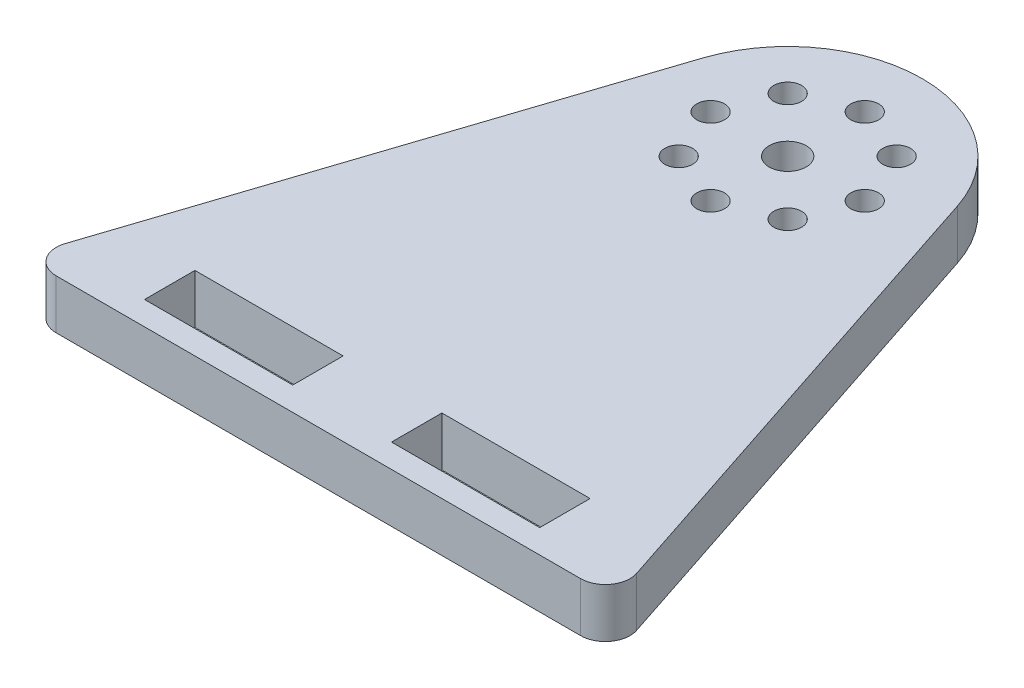
SolidWorks part; units mm, degrees
ref_plane "Front Plane" through (0, 0, 0) normal (0, 0, 1) x (1, 0, 0)
ref_plane "Top Plane" through (0, 0, 0) normal (0, 1, 0) x (1, 0, 0)
ref_plane "Right Plane" through (0, 0, 0) normal (1, 0, 0) x (0, 0, -1)
sketch "Sketch1" plane through (0, 0, 0) normal (0, 1, 0) x (1, 0, 0)
  line L0 (0, 0) -> (0, -60.325) construction
  line L1 (-38.1, -60.325) -> (38.1, -60.325)
  line L2 (0, 0) -> (-38.1, -60.325) construction
  line L3 (0, 0) -> (38.1, -60.325) construction
  line L4 (-46.9823, 0) -> (46.9823, 0) construction
  line L5 (-38.1, -60.325) -> (-16.4346, 5.4161)
  line L6 (38.1, -60.325) -> (16.4346, 5.4161)
  line L7 (34.961, -50.8) -> (-34.961, -50.8) construction
  line L8 (6.35, -50.8) -> (6.35, -57.277)
  line L9 (-25.4, -50.8) -> (-6.35, -50.8)
  line L10 (-25.4, -50.8) -> (-25.4, -57.277)
  line L11 (-25.4, -57.277) -> (-6.35, -57.277)
  line L12 (-6.35, -50.8) -> (-6.35, -57.277)
  line L13 (25.4, -57.277) -> (6.35, -57.277)
  line L14 (25.4, -50.8) -> (25.4, -57.277)
  line L15 (25.4, -50.8) -> (6.35, -50.8)
  circle A0 centre (0, 0) radius 2.3813
  circle A1 centre (-9.906, 0) radius 1.7859
  circle A2 centre (-7.0046, 7.0046) radius 1.7859
  circle A3 centre (0, 9.906) radius 1.7859
  circle A4 centre (7.0046, 7.0046) radius 1.7859
  circle A5 centre (9.906, 0) radius 1.7859
  circle A6 centre (7.0046, -7.0046) radius 1.7859
  circle A7 centre (0, -9.906) radius 1.7859
  circle A8 centre (-7.0046, -7.0046) radius 1.7859
  circle A9 centre (0, 0) radius 17.3041 construction
  arc A10 (-16.4346, 5.4161) -> (16.4346, 5.4161) centre (0, 0) cw
  point P3 (0, 0)
  point P7 (0, -60.325)
  point P11 (0, 0)
  point P29 (0, 0)
  point P34 (0, -50.8)
  dimension "D3" = 4.7625
  dimension "D4" = 3.5719
  dimension "D7" = 9.525
  dimension "D1" = 60.325
  dimension "D2" = 76.2
  dimension "D5" = 9.906
  dimension "D8" = 6.477
  dimension "D9" = 6.35
  dimension "D10" = 19.05
  dimension "D6" = 8
extrude "Boss-Extrude1" add sketch "Sketch1" along normal blind 6.35
fillet "Fillet1" radius 3.175 2 edges at (38.1, 3.175, 60.325) (-38.1, 3.175, 60.325)
